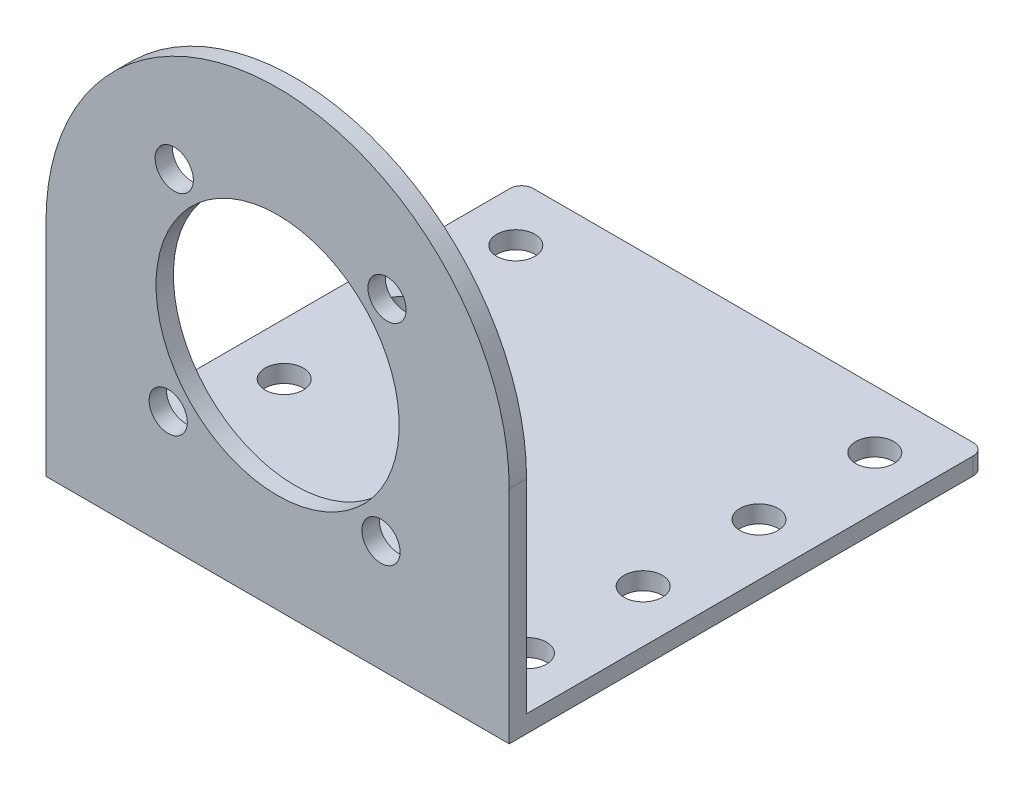
SolidWorks part; units mm, degrees
ref_plane "Front Plane" through (0, 0, 0) normal (0, 0, 1) x (1, 0, 0)
ref_plane "Top Plane" through (0, 0, 0) normal (0, 1, 0) x (1, 0, 0)
ref_plane "Right Plane" through (0, 0, 0) normal (1, 0, 0) x (0, 0, -1)
sketch "Sketch2" plane through (0, 0, 0) normal (1, 0, 0) x (0, 0, -1)
  line L1 (-36.8894, 36.5355) -> (-35.3894, 36.5355)
  line L2 (-36.8894, 36.5355) -> (-36.8894, -2.5345)
  line L3 (-36.8894, -2.5345) -> (-35.3894, -2.5345)
  line L4 (-35.3894, 36.5355) -> (-35.3894, -2.5345)
  line L5 (-36.8894, -2.5345) -> (4.1796, -2.5345)
  line L6 (-36.8894, -2.5345) -> (-36.8894, -1.0345)
  line L7 (-36.8894, -1.0345) -> (4.1796, -1.0345)
  line L8 (4.1796, -2.5345) -> (4.1796, -1.0345)
  dimension "D1" = 1.5
  dimension "D2" = 1.5
  dimension "D3" = 39.07
  dimension "D4" = 41.069
extrude "Boss-Extrude1" add sketch "Sketch2" along normal blind 40 contours L3 L4 L1 L2 | L5 L8 L7 L6
sketch "Sketch3" plane through (0, -1.0345, 0) normal (0, 1, 0) x (1, 0, 0)
  line L0 (40, 4.1796) -> (0, 4.1796) construction
  line L1 (0, -35.3894) -> (0, 4.1796) construction
  line L2 (40, -35.3894) -> (40, 4.1796) construction
  circle A0 centre (4.5, -30.8204) radius 1.65
  circle A1 centre (4.5, -20.8204) radius 1.65
  circle A2 centre (4.5, -10.8204) radius 1.65
  circle A3 centre (4.5, -0.8204) radius 1.65
  circle A4 centre (35.5, -30.8204) radius 1.65
  circle A5 centre (35.5, -20.8204) radius 1.65
  circle A6 centre (35.5, -10.8204) radius 1.65
  circle A7 centre (35.5, -0.8204) radius 1.65
  dimension "D1" = 3.3
  dimension "D2" = 5
  dimension "D3" = 10
  dimension "D4" = 10
  dimension "D5" = 10
  dimension "D6" = 5
  dimension "D7" = 10
  dimension "D8" = 10
  dimension "D9" = 30
  dimension "D10" = 4.5
  dimension "D11" = 4.5
  dimension "D12" = 4.5
  dimension "D13" = 4.5
  dimension "D14" = 4.5
  dimension "D15" = 4.5
extrude "Cut-Extrude1" cut sketch "Sketch3" against normal blind 40
sketch "Sketch4" plane through (0, 0, 35.3894) normal (0, 0, -1) x (-1, 0, 0)
  circle A0 centre (-20, 16.5355) radius 10.5
  circle A1 centre (-20, 16.5355) radius 13
  circle A2 centre (-29.4484, 25.4645) radius 1.65
  circle A3 centre (-10.5516, 7.6065) radius 1.65
  circle A4 centre (-28.929, 7.0871) radius 1.65
  circle A5 centre (-11.071, 25.984) radius 1.65
  arc A6 (-40, 16.5355) -> (0, 16.5355) centre (-20, 16.5355) cw
  line M2 (0, -1.0345) -> (0, 36.5355)
  line M3 (0, 36.5355) -> (-40, 36.5355)
  line M4 (-40, 36.5355) -> (-40, -1.0345)
  dimension "D1" = 21
  dimension "D4" = 26
  dimension "D5" = 3.3
  dimension "D9" = 20
  dimension "D2" = 19.07
  dimension "D3" = 20
  dimension "D6" = 90
  dimension "D7" = 90
  dimension "D8" = 90
  dimension "D10" = 40
extrude "Cut-Extrude2" cut sketch "Sketch4" against normal blind 40 contours A0 | A1 A4 | A1 A4 | A1 A3 | A1 A3 | A6 M4 M3 | A6 M3 M2 | A1 A5 | A1 A5 | A1 A2 | A1 A2 region at (20, 16.5355, 35.3894) region at (11.5647, 25.4615, 35.3894) region at (10.6032, 26.479, 35.3894) region at (10.0566, 7.1387, 35.3894) region at (11.074, 8.1002, 35.3894) region at (28.926, 24.9708, 35.3894) region at (29.9434, 25.9323, 35.3894) region at (29.3968, 6.5921, 35.3894) region at (28.4353, 7.6095, 35.3894) region at (35.5326, 32.0682, 35.3894) region at (4.4674, 32.0682, 35.3894)
fillet "Fillet1" radius 1 2 edges at (0, -1.7845, -4.1796) (40, -1.7845, -4.1796)
